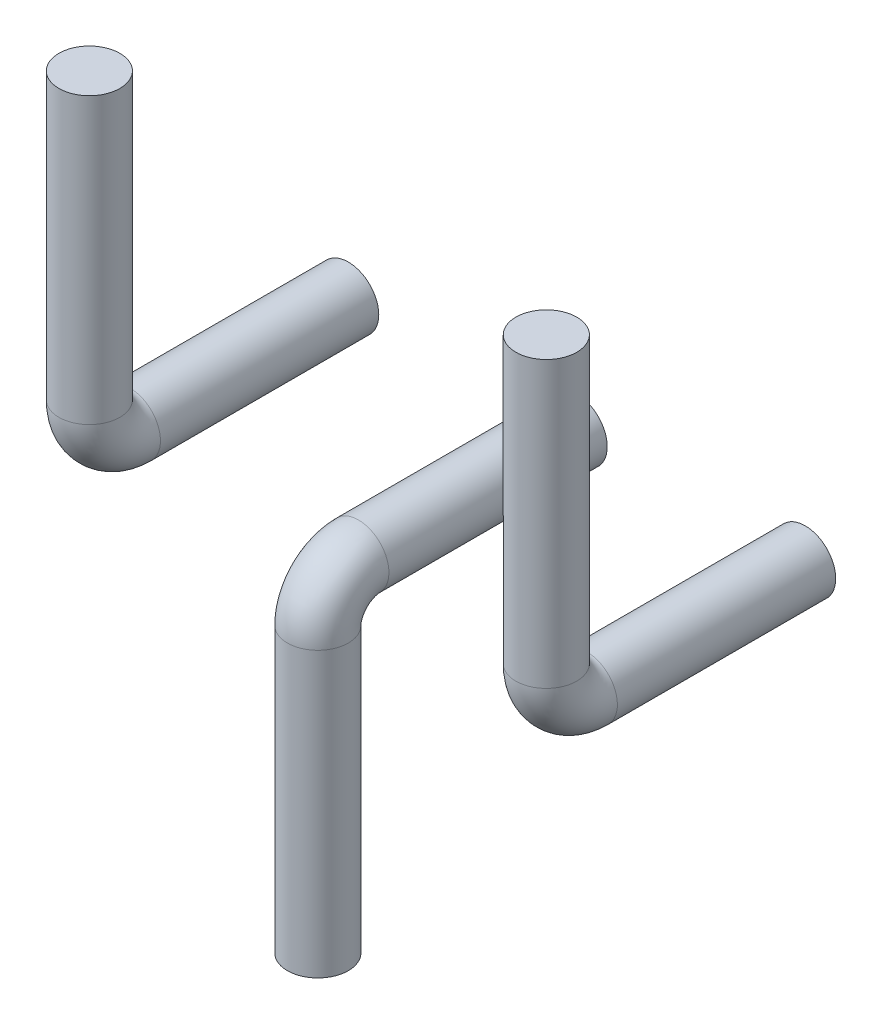
SolidWorks part; units mm, degrees
ref_plane "Piano frontale" through (0, 0, 0) normal (0, 0, 1) x (1, 0, 0)
ref_plane "Piano superiore" through (0, 0, 0) normal (0, 1, 0) x (1, 0, 0)
ref_plane "Piano destro" through (0, 0, 0) normal (1, 0, 0) x (0, 0, -1)
sketch "Schizzo2" plane through (-55, -0.0508, 0) normal (-1, 0, 0) x (0, 0, 1)
  line L0 (0, 0) -> (21.5, 0)
  line L2 (25.5, 32.0508) -> (25.5, 4)
  arc A1 (25.5, 4) -> (21.5, 0) centre (21.5, 4) cw
  dimension "D1" = 4
sketch "Schizzo3" plane through (0, 0, 0) normal (0, 0, 1) x (1, 0, 0)
  circle A0 centre (-55, -0.0508) radius 3
  circle A1 centre (-10, -0.0508) radius 3
sweep "Sweep1" add profiles "Schizzo3" path "Schizzo2"
sketch "Schizzo4" plane through (-32.5, -0.0508, 0) normal (-1, 0, 0) x (0, 0, 1)
  line L0 (0, 0) -> (21.5, 0)
  line L2 (20.5, -31.9492) -> (30.5, -31.9492) construction
  line L3 (25.5, -31.9492) -> (25.5, -4)
  arc A0 (21.5, 0) -> (25.5, -4) centre (21.5, -4) cw
  dimension "D1" = 4
sketch "Schizzo5" plane through (0, 0, 0) normal (0, 0, 1) x (1, 0, 0)
  circle A0 centre (-32.5, -0.0508) radius 3
sweep "Sweep2" add profiles "Schizzo5" path "Schizzo4"
